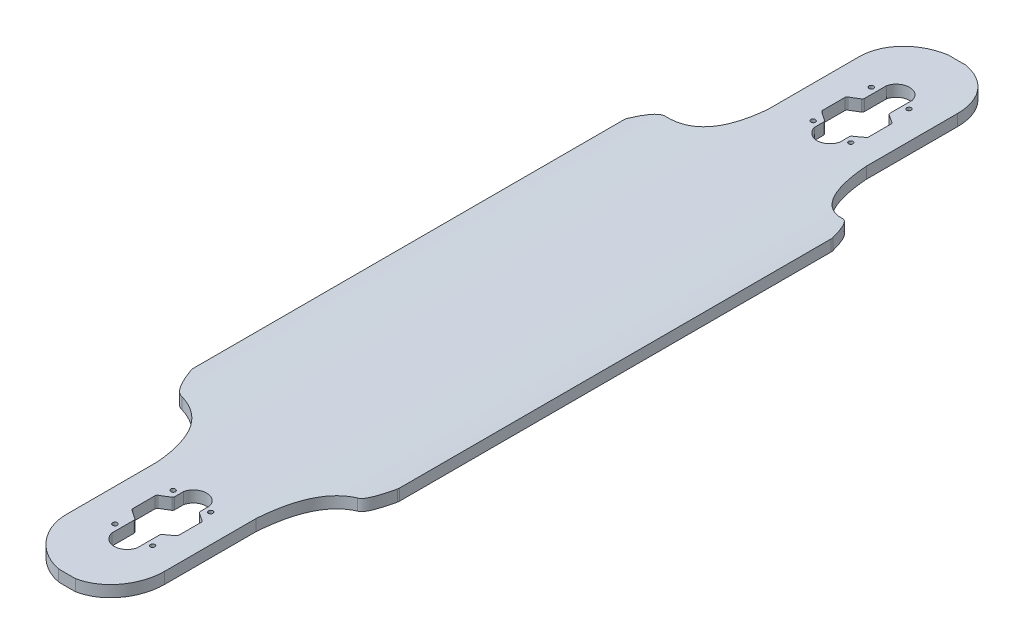
SolidWorks part; units mm, degrees
material "Maple"
ref_plane "Front Plane" through (0, 0, 0) normal (0, 0, 1) x (1, 0, 0)
ref_plane "Top Plane" through (0, 0, 0) normal (0, 1, 0) x (1, 0, 0)
ref_plane "Right Plane" through (0, 0, 0) normal (1, 0, 0) x (0, 0, -1)
sketch "Sketch1" plane through (0, 0, 0) normal (0, 0, 1) x (1, 0, 0)
  line L0 (0, 0) -> (230.1875, 0)
  line L1 (115.0937, 0) -> (115.0937, -12.7)
  line L2 (230.1875, 0) -> (230.1875, -12.7)
  line L3 (0, 0) -> (0, -12.7)
  arc A0 (230.1875, 0) -> (0, 0) centre (115.0938, 515.1686) cw
  arc A1 (230.1875, -12.7) -> (0, -12.7) centre (115.0938, 502.4686) cw
  point P6 (115.0937, -12.7)
  dimension "D1" = 2
extrude "Boss-Extrude1" add sketch "Sketch1" along normal blind 482.6 contours A1 L2 A0 L3 region at (115.0938, -14.8372, 0)
sketch "Sketch2" plane through (0, 0, 0) normal (0, 0, -1) x (-1, 0, 0)
  line L0 (-230.1875, 0) -> (-230.1875, -12.7)
  line L1 (0, 0) -> (0, -12.7)
  line L4 (-60.325, -19.05) -> (-60.325, -9.8511)
  line L5 (-169.8625, -19.05) -> (-169.8625, -9.8511)
  line L6 (-169.8625, -19.05) -> (-169.8625, -22.5511)
  line L7 (-60.325, -22.5511) -> (-60.325, -19.05)
  arc A0 (-230.1875, 0) -> (0, 0) centre (-115.0938, 515.1686) ccw
  arc A1 (-230.1875, -12.7) -> (0, -12.7) centre (-115.0938, 502.4686) ccw
  point P15 (-115.0938, -19.05)
  arc M1 (-230.1875, -12.7) -> (0, -12.7) centre (-115.0938, 502.4686) ccw
  line M2 (0, -12.7) -> (0, 0)
  arc M3 (0, 0) -> (-230.1875, 0) centre (-115.0938, 515.1686) cw
  line M4 (-230.1875, 0) -> (-230.1875, -12.7)
extrude "Boss-Extrude2" add sketch "Sketch2" along normal blind 98.425 contours L6 L5 M3 M4 M1 | L7 L4 M1 M2 M3 region at (200.025, -11.8738, 0) region at (30.1625, -11.8738, 0)
sketch "Sketch3" plane through (0, 0, 0) normal (0, 0, -1) x (-1, 0, 0)
  line L0 (-230.1875, -12.7) -> (-230.1875, 0)
  line L1 (0, 0) -> (0, -12.7)
  line L2 (-169.8625, -9.8511) -> (-169.8625, -22.5511)
  line L3 (-60.325, -9.8511) -> (-60.325, -22.5511)
  arc A0 (-230.1875, 0) -> (0, 0) centre (-115.0937, 515.1686) ccw
  arc A1 (-230.1875, -12.7) -> (0, -12.7) centre (-115.0938, 502.4686) ccw
  arc M1 (-169.8625, -22.5511) -> (-60.325, -22.5511) centre (-115.0938, 502.4686) ccw
  line M2 (-60.325, -22.5511) -> (-60.325, -9.8511)
  arc M3 (-60.325, -9.8511) -> (-169.8625, -9.8511) centre (-115.0938, 515.1686) cw
  line M4 (-169.8625, -9.8511) -> (-169.8625, -22.5511)
extrude "Boss-Extrude3" add sketch "Sketch3" along normal blind 254 contours M4 M1 M2 M3 region at (115.0938, -18.1014, 0)
sketch "Sketch4" plane through (0, 0, 482.6) normal (0, 0, 1) x (1, 0, 0)
  line L0 (0, 0) -> (0, -12.7)
  line L1 (230.1875, -12.7) -> (230.1875, 0)
  line L2 (60.325, -22.5511) -> (60.325, -9.8511)
  line L3 (169.8625, -22.5511) -> (169.8625, -9.8511)
  arc A0 (0, 0) -> (230.1875, 0) centre (115.0938, 515.1686) ccw
  arc A1 (0, -12.7) -> (230.1875, -12.7) centre (115.0938, 502.4686) ccw
  point P15 (115.0937, -19.05)
  arc M1 (0, -12.7) -> (230.1875, -12.7) centre (115.0938, 502.4686) ccw
  arc M3 (230.1875, 0) -> (0, 0) centre (115.0938, 515.1686) cw
extrude "Boss-Extrude4" add sketch "Sketch4" along normal blind 254 contours L3 L2 M1 M3 region at (115.0937, -18.1014, 482.6)
sketch "Sketch5" plane through (0, 0, 482.6) normal (0, 0, 1) x (1, 0, 0)
  line L0 (0, 0) -> (0, -12.7)
  line L1 (60.325, -9.8511) -> (60.325, -22.5511)
  line L2 (230.1875, 0) -> (230.1875, -12.7)
  line L3 (169.8625, -9.8511) -> (169.8625, -22.5511)
  arc A0 (0, 0) -> (230.1875, 0) centre (115.0938, 515.1686) ccw
  arc A1 (0, -12.7) -> (230.1875, -12.7) centre (115.0938, 502.4686) ccw
  arc M1 (0, -12.7) -> (60.325, -22.5511) centre (115.0938, 502.4686) ccw
  line M2 (60.325, -22.5511) -> (60.325, -9.8511)
  arc M3 (60.325, -9.8511) -> (0, 0) centre (115.0938, 515.1686) cw
  line M4 (0, 0) -> (0, -12.7)
extrude "Boss-Extrude5" add sketch "Sketch5" along normal blind 98.425 contours M4 M1 M2 M3 | L3 A1 L2 A0 region at (30.1625, -11.8738, 482.6) region at (200.025, -11.8738, 482.6)
ref_plane "Plane1" through (0, 0, 0) normal (0, -1, 0) x (-1, 0, 0)
sketch "Sketch6" plane through (0, 0, 0) normal (0, -1, 0) x (-1, 0, 0)
  line L0 (-115.0937, -736.6) -> (-115.0937, -482.6) construction
  line L1 (-169.8625, -736.6) -> (-60.325, -736.6) construction
  line L2 (-115.0938, 254) -> (-115.0937, 0) construction
  line L3 (-60.325, 254) -> (-169.8625, 254) construction
  line L4 (-230.1875, -482.6) -> (0, -482.6) construction
  line L5 (0, -581.025) -> (0, 98.425) construction
  line L6 (-230.1875, 0) -> (0, 0) construction
  line L7 (-60.325, -581.025) -> (0, -482.6) construction
  line L8 (-60.325, -736.6) -> (-60.325, -581.025) construction
  line L9 (-60.325, -682.625) -> (-169.8625, -682.625) construction
  line L10 (-169.8625, -736.6) -> (-169.8625, -581.025) construction
  line L11 (-169.8625, -581.025) -> (-230.1875, -482.6) construction
  line L12 (-60.325, 254) -> (-60.325, 98.425) construction
  line L13 (-60.325, 200.025) -> (-169.8625, 200.025) construction
  line L14 (-169.8625, 254) -> (-169.8625, 98.425) construction
  line L15 (-30.1625, -531.8125) -> (-200.025, -531.8125) construction
  line L16 (-230.1875, 0) -> (-169.8625, 98.425) construction
  line L17 (-60.325, 98.425) -> (0, 0) construction
  line L18 (-200.025, 49.2125) -> (-30.1625, 49.2125) construction
  line L19 (-30.1625, -531.8125) -> (-230.1875, -482.6) construction
  line L20 (-200.025, -531.8125) -> (0, -482.6) construction
  line L21 (0, 0) -> (-200.025, 49.2125) construction
  line L22 (-30.1625, 49.2125) -> (-230.1875, 0) construction
  line L23 (-230.1875, -510.9167) -> (0, -510.9167) construction
  line L24 (-230.1875, 28.3167) -> (0, 28.3167) construction
  line L25 (0, 0) -> (-8.6777, 28.3167) construction
  line L26 (-17.3554, -510.9167) -> (-8.6777, -510.9167) construction
  line L27 (-221.5098, 28.3167) -> (-230.1875, 0) construction
  line L28 (-8.6777, -510.9167) -> (0, -482.6) construction
  line L29 (-230.1875, -482.6) -> (-221.5098, -510.9167) construction
  line L30 (-212.8321, -510.9167) -> (-221.5098, -510.9167) construction
  line L31 (-8.6777, -510.9167) -> (0, -482.6) construction
  line L32 (-221.5098, -510.9167) -> (-230.1875, -482.6) construction
  line L33 (-17.3554, 28.3167) -> (-8.6777, 28.3167) construction
  line L34 (-8.6777, 28.3167) -> (0, 0) construction
  line L35 (-212.8321, 28.3167) -> (-221.5098, 28.3167) construction
  line L36 (-221.5098, 28.3167) -> (-230.1875, 0) construction
  line L38 (-60.325, -581.025) -> (0, -581.025)
  line L39 (0, -581.025) -> (0, -510.9167)
  line L40 (-60.325, -682.625) -> (-60.325, -736.6)
  line L41 (-60.325, -736.6) -> (-169.8625, -736.6)
  line L42 (-169.8625, -736.6) -> (-169.8625, -682.625)
  line L43 (-169.8625, -581.025) -> (-230.1875, -581.025)
  line L44 (-230.1875, -581.025) -> (-230.1875, -510.9167)
  line L45 (-230.1875, 0) -> (-230.1875, 98.425)
  line L46 (-230.1875, 98.425) -> (-169.8625, 98.425)
  line L47 (-169.8625, 200.025) -> (-169.8625, 254)
  line L48 (-169.8625, 254) -> (-60.325, 254)
  line L49 (-60.325, 254) -> (-60.325, 200.025)
  line L50 (-60.325, 98.425) -> (0, 98.425)
  line L51 (0, 98.425) -> (0, 0)
  line L52 (-230.1875, -482.6) -> (-230.1875, -510.9167)
  line L53 (0, -482.6) -> (0, -510.9167)
  arc A0 (-60.325, -682.625) -> (-169.8625, -682.625) centre (-115.0937, -682.625) cw
  arc A1 (-60.325, 200.025) -> (-169.8625, 200.025) centre (-115.0938, 200.025) ccw
  spline S0 degree 2 poles (-60.325, -581.025) (-55.0487, -517.0259) (-17.3554, -510.9167) knots 0 0 0 0.825721 0.825721 0.825721
  spline S1 degree 2 poles (-169.8625, -581.025) (-175.1388, -517.0259) (-212.8321, -510.9167) knots 0 0 0 0.825721 0.825721 0.825721
  spline S2 degree 2 poles (-169.8625, 98.425) (-175.1388, 34.4259) (-212.8321, 28.3167) knots 0 0 0 0.825721 0.825721 0.825721
  spline S3 degree 2 poles (-60.325, 98.425) (-55.0487, 34.4259) (-17.3554, 28.3167) knots 0 0 0 0.825721 0.825721 0.825721
  spline S4 degree 2 poles (-17.3554, -510.9167) (-8.6777, -510.9167) (0, -482.6) knots 0 0 0 1 1 1
  spline S5 degree 2 poles (-212.8321, -510.9167) (-221.5098, -510.9167) (-230.1875, -482.6) knots 0 0 0 1 1 1
  spline S6 degree 2 poles (-17.3554, 28.3167) (-8.6777, 28.3167) (0, 0) knots 0 0 0 1 1 1
  spline S7 degree 2 poles (-212.8321, 28.3167) (-221.5098, 28.3167) (-230.1875, 0) knots 0 0 0 1 1 1
  point P13 (-115.0937, -482.6)
  point P17 (-115.0937, 0)
  point P43 (-115.0938, -510.9167)
  point P44 (-17.3554, -510.9167)
  point P45 (-115.0938, 28.3167)
  point P49 (-115.0938, -510.9167)
  point P51 (-115.0938, 28.3167)
  point P53 (-212.8321, -510.9167)
  point P54 (-212.8321, 28.3167)
  point P55 (-17.3554, 28.3167)
extrude "Cut-Extrude1" cut sketch "Sketch6" along normal blind 98.425 contours L40 A0 L41 | L41 A0 L42 | S1 S5 L52 L44 L43 | S4 S0 L38 L39 L53 | S3 S6 L51 L50 | S7 S2 L46 L45 | A1 L48 L47 | A1 L49 L48 region at (25.0997, 0, 547.5668) region at (158.3996, 0, 724.4055) region at (71.7879, 0, 724.4055) region at (205.0878, 0, 547.5668) region at (205.0878, 0, -64.9668) region at (71.7879, 0, -241.8055) region at (158.3996, 0, -241.8055) region at (25.0997, 0, -64.9668)
sketch "Sketch8" plane through (0, 0, 0) normal (0, -1, 0) x (-1, 0, 0)
  line L0 (-60.325, 98.425) -> (-169.8625, 98.425) construction
  line L1 (0, 0) -> (-230.1875, 0) construction
  line L2 (-100.8698, 189.865) -> (-100.8698, 163.957)
  line L3 (-115.0938, 98.425) -> (-115.0937, 0)
  line L4 (0, -482.6) -> (-230.1875, -482.6)
  line L5 (0, -241.3) -> (-230.1875, -241.3)
  line L6 (0, -482.6) -> (0, 0) construction
  line L7 (-230.1875, -482.6) -> (-230.1875, 0) construction
  line L8 (-100.8698, 163.957) -> (-89.4398, 156.337)
  line L9 (-89.4398, 156.337) -> (-89.4398, 128.905)
  line L10 (-89.4398, 128.905) -> (-100.8698, 121.285)
  line L11 (-100.8698, 121.285) -> (-100.8698, 109.855)
  line L12 (-129.3177, 109.855) -> (-129.3177, 121.285)
  line L13 (-129.3177, 121.285) -> (-140.7477, 128.905)
  line L14 (-140.7477, 128.905) -> (-140.7477, 156.337)
  line L15 (-140.7477, 156.337) -> (-129.3177, 163.957)
  line L16 (-129.3177, 163.957) -> (-129.3177, 189.865)
  line L17 (-115.0938, 98.425) -> (-115.0938, 114.935) construction
  line L18 (-115.0938, 201.295) -> (-115.0938, 179.705) construction
  line L19 (-94.1388, 179.705) -> (-136.0488, 179.705) construction
  line L20 (-94.1388, 114.935) -> (-136.0488, 114.935) construction
  line L21 (-94.1387, -597.535) -> (-136.0487, -597.535) construction
  line L22 (-94.1387, -662.305) -> (-136.0487, -662.305) construction
  line L23 (-115.0937, -683.895) -> (-115.0937, -662.305) construction
  line L24 (-115.0937, -581.025) -> (-115.0937, -597.535) construction
  line L25 (-129.3177, -646.557) -> (-129.3177, -672.465)
  line L26 (-140.7477, -638.937) -> (-129.3177, -646.557)
  line L27 (-140.7477, -611.505) -> (-140.7477, -638.937)
  line L28 (-129.3177, -603.885) -> (-140.7477, -611.505)
  line L29 (-129.3177, -592.455) -> (-129.3177, -603.885)
  line L30 (-100.8698, -603.885) -> (-100.8698, -592.455)
  line L31 (-89.4398, -611.505) -> (-100.8698, -603.885)
  line L32 (-89.4398, -638.937) -> (-89.4398, -611.505)
  line L33 (-100.8698, -646.557) -> (-89.4398, -638.937)
  line L34 (-100.8698, -672.465) -> (-100.8698, -646.557)
  arc A0 (-100.8698, 189.865) -> (-129.3177, 189.865) centre (-115.0938, 186.7295) ccw
  arc A1 (-100.8698, 109.855) -> (-129.3177, 109.855) centre (-115.0938, 112.9905) cw
  circle A2 centre (-136.0488, 179.705) radius 2.54
  circle A3 centre (-136.0488, 114.935) radius 2.54
  circle A4 centre (-94.1388, 114.935) radius 2.54
  circle A5 centre (-94.1388, 179.705) radius 2.54
  circle A6 centre (-94.1387, -597.535) radius 2.54
  circle A7 centre (-136.0487, -597.535) radius 2.54
  circle A8 centre (-136.0487, -662.305) radius 2.54
  arc A9 (-100.8698, -592.455) -> (-129.3177, -592.455) centre (-115.0937, -595.5905) ccw
  arc A10 (-100.8698, -672.465) -> (-129.3177, -672.465) centre (-115.0937, -669.3295) cw
  circle A11 centre (-94.1387, -662.305) radius 2.54
  point P26 (-115.0937, 189.865)
  point P29 (-115.0938, 201.295)
  point P30 (-115.0938, 98.425)
  point P42 (-115.0938, 179.705)
  point P46 (-115.0938, 114.935)
  point P47 (-100.8698, 163.957)
  point P48 (-89.4398, 156.337)
  point P49 (-89.4398, 128.905)
  point P50 (-100.8698, 121.285)
  point P51 (-100.8698, 109.855)
  point P52 (-129.3177, 109.855)
  point P53 (-129.3177, 121.285)
  point P54 (-140.7477, 128.905)
  point P55 (-140.7477, 156.337)
  point P56 (-129.3177, 163.957)
  point P57 (-129.3177, 189.865)
  point P58 (-100.8698, 189.865)
  point P59 (-100.8698, 163.957)
  point P60 (-89.4398, 156.337)
  point P87 (-115.0937, -672.465)
extrude "Cut-Extrude2" cut sketch "Sketch8" along normal blind 30.48 contours A1 L11 L10 L9 L8 L2 A0 L16 L15 L14 L13 L12 | A4 | A10 L34 L33 L32 L31 L30 A9 L29 L28 L27 L26 L25 | A2 | A5 | A3 | A11 | A8 | A6 | A7 region at (115.0937, 0, -148.2319) region at (115.0937, 0, 630.8319) region at (94.1388, 0, -114.935)
fillet "Fillet2" radius 2.54 16 edges at (100.8698, -18.8583, -121.285) (89.4398, -18.4262, -128.905) (89.4398, -18.4262, -156.337) (100.8698, -18.8583, -163.957) (129.3177, -18.8583, -121.285) (140.7477, -18.4262, -128.905) (140.7477, -18.4262, -156.337) (129.3177, -18.8583, -163.957) (140.7477, -18.4262, 638.937) (140.7477, -18.4262, 611.505) (89.4398, -18.4262, 638.937) (89.4398, -18.4262, 611.505) (129.3177, -18.8583, 646.557) (129.3177, -18.8583, 603.885) (100.8698, -18.8583, 646.557) (100.8698, -18.8583, 603.885)
fillet "Fillet1" radius 7.62 4 edges at (0, -6.35, 0) (0, -6.35, 482.6) (230.1875, -6.35, 0) (230.1875, -6.35, 482.6)
